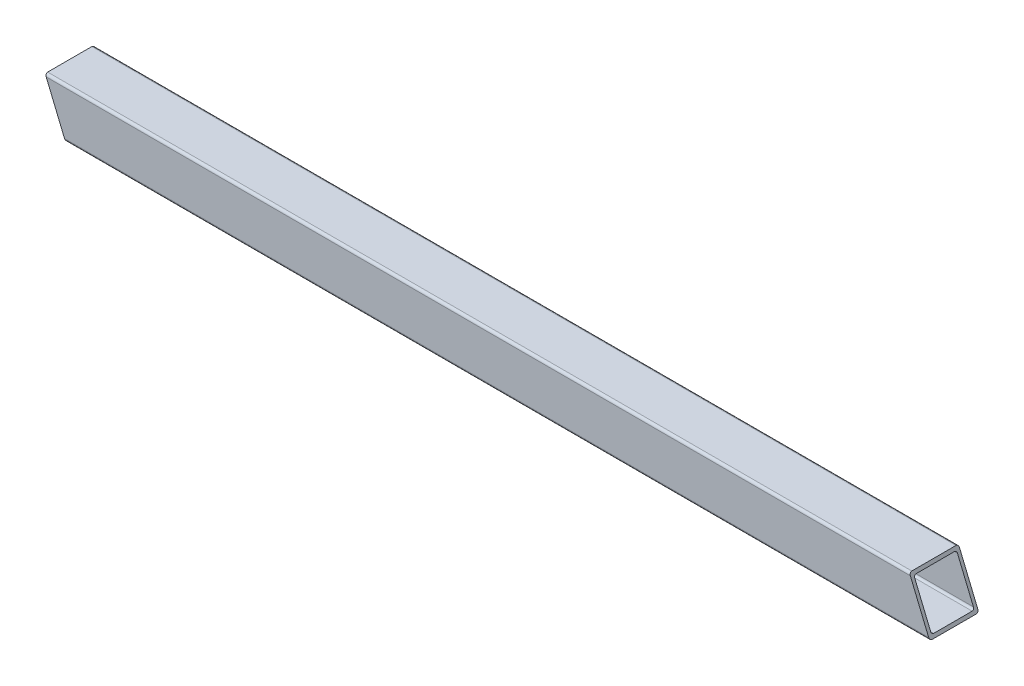
SolidWorks part; units mm, degrees
ref_plane "Front" through (0, 0, 0) normal (0, 0, 1) x (1, 0, 0)
ref_plane "Top" through (0, 0, 0) normal (0, 1, 0) x (1, 0, 0)
ref_plane "Right" through (0, 0, 0) normal (1, 0, 0) x (0, 0, -1)
sketch "Sketch1" plane through (0, 0, 0) normal (1, 0, 0) x (0, 0, -1)
  line L0 (-11.049, 0) -> (-12.7, 0) construction
  line L1 (11.43, -12.7) -> (-11.43, -12.7) construction
  line L2 (12.7, -11.43) -> (12.7, 11.43) construction
  line L3 (11.43, 12.7) -> (-11.43, 12.7) construction
  line L4 (-12.7, -11.43) -> (-12.7, 11.43) construction
  line L5 (12.7, -12.7) -> (-12.7, 12.7) construction
  line L6 (12.7, 12.7) -> (-12.7, -12.7) construction
  line L7 (9.9441, 11.049) -> (-9.9441, 11.049) construction
  line L8 (11.049, 9.9441) -> (11.049, -9.9441) construction
  line L9 (9.9441, -11.049) -> (-9.9441, -11.049) construction
  line L10 (-11.049, 9.9441) -> (-11.049, -9.9441) construction
  line L11 (11.049, 11.049) -> (-11.049, -11.049) construction
  line L12 (11.049, -11.049) -> (-11.049, 11.049) construction
  line L13 (0, -11.049) -> (0, -12.7) construction
  line L14 (11.049, -9.9441) -> (11.049, -12.7) construction
  line L15 (11.049, 0) -> (12.7, 0) construction
  line L16 (11.049, -12.7) -> (12.7, -12.7) construction
  arc A0 (-9.9441, -11.049) -> (-11.049, -9.9441) centre (-9.9441, -9.9441) cw construction
  arc A1 (11.049, -9.9441) -> (9.9441, -11.049) centre (9.9441, -9.9441) cw construction
  arc A2 (9.9441, 11.049) -> (11.049, 9.9441) centre (9.9441, 9.9441) cw construction
  arc A3 (-9.9441, 11.049) -> (-11.049, 9.9441) centre (-9.9441, 9.9441) ccw construction
  arc A4 (11.43, -12.7) -> (12.7, -11.43) centre (11.43, -11.43) ccw construction
  arc A5 (12.7, 11.43) -> (11.43, 12.7) centre (11.43, 11.43) ccw construction
  arc A6 (-11.43, 12.7) -> (-12.7, 11.43) centre (-11.43, 11.43) ccw construction
  arc A7 (-11.43, -12.7) -> (-12.7, -11.43) centre (-11.43, -11.43) cw construction
  point P0 (0, 0)
  point P6 (0, 0)
  dimension "D2" = 1.1049
  dimension "D3" = 1.27
  dimension "Outside Width" = 25.4
  dimension "Ouside Height" = 25.4
  dimension "Inside Height" = 22.098
  dimension "Wall Thickness" = 1.651
sketch "Sketch2" plane through (0, 0, 0) normal (0, 0, 1) x (1, 0, 0)
  line L0 (-228.6, 0) -> (228.6, 0) construction
  point P3 (-204.851, 0)
  point P4 (204.851, 0)
  dimension "Length" = 457.2
  dimension "D1" = 23.749
  dimension "D2" = 23.749
sketch "Sketch4" plane through (0, 0, 0) normal (1, 0, 0) x (0, 0, -1)
  line L8 (12.7, -11.43) -> (12.7, 11.43)
  line L9 (11.43, 12.7) -> (-11.43, 12.7)
  line L10 (-12.7, -11.43) -> (-12.7, 11.43)
  line L11 (11.43, -12.7) -> (-11.43, -12.7)
  line L12 (11.049, 9.9441) -> (11.049, -9.9441)
  line L13 (9.9441, -11.049) -> (-9.9441, -11.049)
  line L14 (-11.049, 9.9441) -> (-11.049, -9.9441)
  line L15 (9.9441, 11.049) -> (-9.9441, 11.049)
  arc A8 (12.7, 11.43) -> (11.43, 12.7) centre (11.43, 11.43) ccw
  arc A9 (-11.43, 12.7) -> (-12.7, 11.43) centre (-11.43, 11.43) ccw
  arc A10 (-12.7, -11.43) -> (-11.43, -12.7) centre (-11.43, -11.43) ccw
  arc A11 (11.43, -12.7) -> (12.7, -11.43) centre (11.43, -11.43) ccw
  arc A12 (9.9441, -11.049) -> (11.049, -9.9441) centre (9.9441, -9.9441) ccw
  arc A13 (-11.049, -9.9441) -> (-9.9441, -11.049) centre (-9.9441, -9.9441) ccw
  arc A14 (-9.9441, 11.049) -> (-11.049, 9.9441) centre (-9.9441, 9.9441) ccw
  arc A15 (11.049, 9.9441) -> (9.9441, 11.049) centre (9.9441, 9.9441) ccw
extrude "Boss-Extrude1" add sketch "Sketch4" along normal up to vertex (-228.6 mm away) and the other way up to vertex (-228.6 mm away) up to point (-228.6, 0, 0) other way up to point (228.6, 0, 0)
sketch "Sketch5" plane through (0, 0, 12.7) normal (0, 0, 1) x (1, 0, 0)
  line L4 (228.6, -12.7) -> (228.6, 12.7)
  line L5 (228.6, 12.7) -> (218.079, 12.7)
  line L6 (228.6, 12.7) -> (-228.6, 12.7) construction
  line L7 (218.079, 12.7) -> (228.6, -12.7)
  line L10 (-228.6, -12.7) -> (-228.6, 12.7)
  line L11 (-228.6, 12.7) -> (-218.079, -12.7)
  line L12 (228.6, -12.7) -> (-228.6, -12.7) construction
  line L13 (-218.079, -12.7) -> (-228.6, -12.7)
  dimension "D1" = 22.5
  dimension "D2" = 22.5
extrude "Cut-Extrude1" cut sketch "Sketch5" against normal through all
equation "\"D3@Sketch1\"=\"Outside Width@Sketch1\"*.05"
equation "\"D2@Sketch1\" = \"Inside Height@Sketch1\" * .05"
equation "\"D1@Sketch2\"=\"Outside Width@Sketch1\"-\"Wall Thickness@Sketch1\""
equation "\"D2@Sketch2\"=\"D1@Sketch2\""
